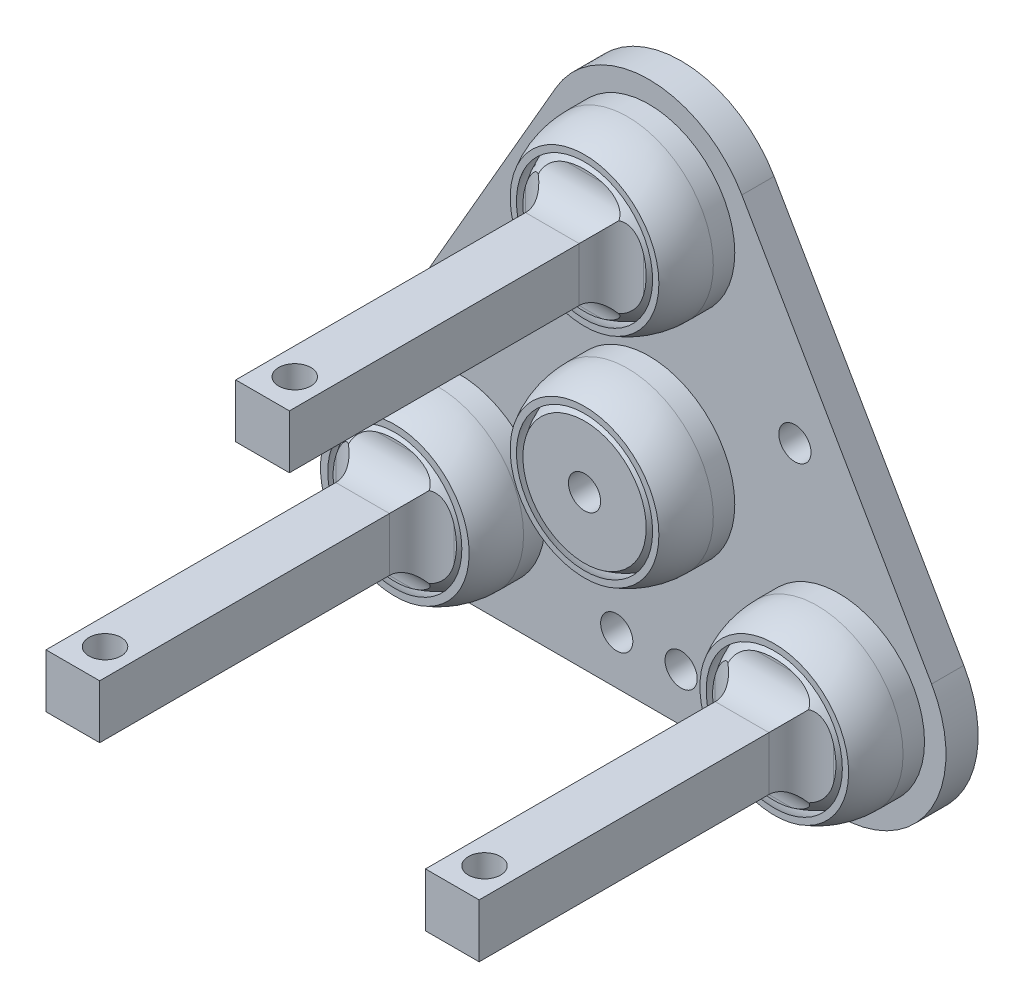
SolidWorks part; units mm, degrees
ref_plane "Front Plane" through (0, 0, 0) normal (0, 0, 1) x (1, 0, 0)
ref_plane "Top Plane" through (0, 0, 0) normal (0, 1, 0) x (1, 0, 0)
ref_plane "Right Plane" through (0, 0, 0) normal (1, 0, 0) x (0, 0, -1)
sketch "Sketch1" plane through (0, 0, 0) normal (0, 0, 1) x (1, 0, 0)
  line L0 (-39.7069, 0) -> (30.2931, 0)
  line L1 (30.2931, 0) -> (-4.7069, 60.6218)
  line L2 (-39.7069, 0) -> (-4.7069, 60.6218)
  dimension "D1" = 70
  dimension "D2" = 60
  dimension "D3" = 60
extrude "Boss-Extrude1" add sketch "Sketch1" along normal blind 3 contours L2 L0 L1 | L2 L0 L1 region at (-4.7069, 20.2073, 0)
sketch "Sketch4" plane through (0, 0, 3) normal (0, 0, 1) x (1, 0, 0)
  line L0 (-4.7069, 60.6218) -> (-4.7069, 40.6218) construction
  line L1 (-39.7069, 0) -> (-22.3864, 10) construction
  line L2 (30.2931, 0) -> (12.9726, 10) construction
  line L3 (-4.7069, 40.6218) -> (-4.7069, 0) construction
  line L4 (-39.7069, 0) -> (30.2931, 0) construction
  line L6 (12.9726, 10) -> (-22.2069, 30.3109) construction
  line L7 (-39.7069, 0) -> (-4.7069, 60.6218) construction
  line L8 (-28.743, 24.6509) -> (-42.7396, 47.6087) construction
  line L9 (-22.3864, 10) -> (12.7931, 30.3109) construction
  circle A0 centre (-22.3864, 10) radius 8
  circle A1 centre (-4.7069, 40.6218) radius 8
  circle A2 centre (12.9726, 10) radius 8
  circle A3 centre (-4.7069, 20.3109) radius 8
  dimension "D3" = 20
  dimension "D6" = 16
  dimension "D7" = 16
  dimension "D8" = 16
  dimension "D9" = 16
  dimension "D1" = 30
  dimension "D2" = 30
  dimension "D4" = 20
  dimension "D5" = 20
extrude "Boss-Extrude2" add sketch "Sketch4" along normal blind 2
sketch "Sketch5" plane through (0, 0, 5) normal (0, 0, 1) x (1, 0, 0)
  line L0 (-4.7069, 48.6218) -> (-4.7069, 32.6218)
  circle A0 centre (-4.7069, 40.6218) radius 8 construction
  circle A1 centre (-4.7069, 40.6218) radius 8 construction
  arc A2 (-4.7069, 48.6218) -> (-4.7069, 32.6218) centre (-4.7069, 40.6218) cw
revolve "Revolve3" add sketch "Sketch5" angle 360 about L0
sketch "Sketch6" plane through (0, 0, 5) normal (0, 0, 1) x (1, 0, 0)
  line L0 (-4.7069, 28.3109) -> (-4.7069, 12.3109)
  circle A0 centre (-4.7069, 20.3109) radius 8 construction
  circle A1 centre (-4.7069, 20.3109) radius 8 construction
  arc A2 (-4.7069, 28.3109) -> (-4.7069, 12.3109) centre (-4.7069, 20.3109) cw
revolve "Revolve4" add sketch "Sketch6" angle 360 about L0
sketch "Sketch7" plane through (0, 0, 5) normal (0, 0, 1) x (1, 0, 0)
  line L0 (-22.3864, 18) -> (-22.3864, 2)
  circle A0 centre (-22.3864, 10) radius 8 construction
  circle A1 centre (-22.3864, 10) radius 8 construction
  arc A2 (-22.3864, 18) -> (-22.3864, 2) centre (-22.3864, 10) cw
revolve "Revolve5" add sketch "Sketch7" angle 360 about L0
sketch "Sketch8" plane through (0, 0, 5) normal (0, 0, 1) x (1, 0, 0)
  line L0 (12.9726, 18) -> (12.9726, 2)
  circle A0 centre (12.9726, 10) radius 8 construction
  circle A1 centre (12.9726, 10) radius 8 construction
  arc A2 (12.9726, 18) -> (12.9726, 2) centre (12.9726, 10) cw
revolve "Revolve6" add sketch "Sketch8" angle 360 about L0
ref_plane "Plane2" through (0, 0, 13) normal (0, 0, -1) x (-1, 0, 0)
sketch "Sketch10" plane through (0, 0, 13) normal (0, 0, -1) x (-1, 0, 0)
  line L1 (34.5189, 52.9418) -> (-25.1051, 52.9418)
  line L2 (34.5189, 52.9418) -> (34.5189, -12.32)
  line L3 (34.5189, -12.32) -> (-25.1051, -12.32)
  line L4 (-25.1051, 52.9418) -> (-25.1051, -12.32)
  line L5 (34.5189, 52.9418) -> (-25.1051, -12.32) construction
  line L6 (34.5189, -12.32) -> (-25.1051, 52.9418) construction
  point P0 (4.7069, 20.3109)
extrude "Cut-Extrude1" cut sketch "Sketch10" along normal blind 4
ref_plane "Plane3" through (0, 0, 5) normal (0, 0, 1) x (1, 0, 0)
sketch "Sketch11" plane through (0, 0, 5) normal (0, 0, 1) x (1, 0, 0)
  line L0 (-4.7069, 48.1218) -> (-4.7069, 33.1218)
  circle A0 centre (-4.7069, 40.6218) radius 8 construction
  arc A1 (-4.7069, 48.1218) -> (-4.7069, 33.1218) centre (-4.7069, 40.6218) cw
  dimension "D2" = 7.5
  dimension "D1" = 15
revolve "Cut-Revolve1" cut sketch "Sketch11" angle 360 about L0
ref_plane "Plane4" through (0, 0, 5) normal (0, 0, 1) x (1, 0, 0)
sketch "Sketch12" plane through (0, 0, 5) normal (0, 0, 1) x (1, 0, 0)
  line L0 (-4.7069, 27.8109) -> (-4.7069, 12.8109)
  circle A0 centre (-4.7069, 20.3109) radius 8 construction
  arc A1 (-4.7069, 27.8109) -> (-4.7069, 12.8109) centre (-4.7069, 20.3109) cw
  dimension "D2" = 7.5
  dimension "D1" = 15
revolve "Cut-Revolve2" cut sketch "Sketch12" angle 360 about L0
ref_plane "Plane5" through (0, 0, 5) normal (0, 0, 1) x (1, 0, 0)
sketch "Sketch13" plane through (0, 0, 5) normal (0, 0, 1) x (1, 0, 0)
  line L0 (12.9726, 17.5) -> (12.9726, 2.5)
  circle A0 centre (12.9726, 10) radius 8 construction
  arc A1 (12.9726, 17.5) -> (12.9726, 2.5) centre (12.9726, 10) cw
  dimension "D1" = 15
  dimension "D2" = 7.5
revolve "Cut-Revolve3" cut sketch "Sketch13" angle 360 about L0
ref_plane "Plane6" through (0, 0, 5) normal (0, 0, 1) x (1, 0, 0)
sketch "Sketch14" plane through (0, 0, 5) normal (0, 0, 1) x (1, 0, 0)
  line L0 (-22.3864, 17.5) -> (-22.3864, 2.5)
  circle A0 centre (-22.3864, 10) radius 8 construction
  arc A1 (-22.3864, 17.5) -> (-22.3864, 2.5) centre (-22.4707, 10) cw
  dimension "D1" = 15
  dimension "D2" = 7.5
revolve "Cut-Revolve4" cut sketch "Sketch14" angle 360 about L0
sketch "Sketch16" plane through (0, 0, 5) normal (0, 0, 1) x (1, 0, 0)
  line L0 (-22.3864, 17) -> (-22.3864, 3)
  circle A0 centre (-22.3864, 10) radius 8 construction
  arc A1 (-22.3864, 17) -> (-22.3864, 3) centre (-22.3864, 10) cw
  dimension "D1" = 14
  dimension "D2" = 7
revolve "Revolve7" add sketch "Sketch16" angle 360 about L0
sketch "Sketch17" plane through (0, 0, 5) normal (0, 0, 1) x (1, 0, 0)
  line L0 (12.9726, 17) -> (12.9726, 3)
  circle A0 centre (12.9726, 10) radius 8 construction
  arc A1 (12.9726, 17) -> (12.9726, 3) centre (12.9726, 10) cw
  dimension "D1" = 14
  dimension "D2" = 7
revolve "Revolve8" add sketch "Sketch17" angle 360 about L0
sketch "Sketch18" plane through (0, 0, 5) normal (0, 0, 1) x (1, 0, 0)
  line L0 (-4.7069, 27.3109) -> (-4.7069, 13.3109)
  circle A0 centre (-4.7069, 20.3109) radius 8 construction
  arc A1 (-4.7069, 27.3109) -> (-4.7069, 13.3109) centre (-4.7069, 20.3109) cw
  dimension "D3" = 7
  dimension "D1" = 14
  dimension "D2" = 7
revolve "Revolve9" add sketch "Sketch18" angle 360 about L0
sketch "Sketch19" plane through (0, 0, 5) normal (0, 0, 1) x (1, 0, 0)
  line L0 (-4.7069, 47.6218) -> (-4.7069, 33.6218)
  circle A0 centre (-4.7069, 40.6218) radius 8 construction
  arc A1 (-4.7069, 47.6218) -> (-4.7069, 33.6218) centre (-4.7069, 40.6218) cw
  dimension "D3" = 7
  dimension "D1" = 14
  dimension "D2" = 7
revolve "Revolve10" add sketch "Sketch19" angle 360 about L0
sketch "Sketch20" plane through (0, 0, 9) normal (0, 0, 1) x (1, 0, 0)
  line L1 (-44.0878, 97.9698) -> (34.674, 97.9698)
  line L2 (-44.0878, 97.9698) -> (-44.0878, -2.8698)
  line L3 (-44.0878, -2.8698) -> (34.674, -2.8698)
  line L4 (34.674, 97.9698) -> (34.674, -2.8698)
  line L5 (-44.0878, 97.9698) -> (34.674, -2.8698) construction
  line L6 (-44.0878, -2.8698) -> (34.674, 97.9698) construction
  circle A0 centre (-4.7069, 40.6218) radius 6.9282 construction
  point P0 (-4.7069, 47.55)
extrude "Cut-Extrude2" cut sketch "Sketch20" along normal blind 11
sketch "Sketch21" plane through (0, 0, 0) normal (0, 0, -1) x (-1, 0, 0)
  line L1 (-26.6658, 56.1395) -> (35.9916, 56.1395)
  line L2 (-26.6658, 56.1395) -> (-26.6658, 1.9303)
  line L3 (-26.6658, 1.9303) -> (35.9916, 1.9303)
  line L4 (35.9916, 56.1395) -> (35.9916, 1.9303)
  line L5 (-26.6658, 56.1395) -> (35.9916, 1.9303) construction
  line L6 (-26.6658, 1.9303) -> (35.9916, 56.1395) construction
  point P0 (4.6629, 29.0349)
extrude "Cut-Extrude3" cut sketch "Sketch21" along normal blind 8
sketch "Sketch22" plane through (0, 0, 3) normal (0, 0, 1) x (1, 0, 0)
  line L2 (-39.7069, 0) -> (30.2931, 0) construction
  line L3 (30.2931, 0) -> (-4.7069, 60.6218) construction
  line L4 (-39.7069, 0) -> (-4.7069, 60.6218) construction
  circle A0 centre (-7.7069, 4.5) radius 1.5
  circle A1 centre (-1.7069, 4.5) radius 1.5
  circle A2 centre (8.896, 28.0609) radius 1.5
  circle A3 centre (-18.3098, 28.0609) radius 1.5
  point P0 (-4.7069, 0)
  point P1 (-4.7069, 0)
  point P4 (12.7931, 30.3109)
  point P16 (-22.2069, 30.3109)
  dimension "D1" = 4.5
  dimension "D3" = 3
  dimension "D4" = 3
  dimension "D7" = 3
  dimension "D8" = 4.5
  dimension "D5" = 3
  dimension "D2" = 4.5
  dimension "D6" = 3
  dimension "D9" = 3
  dimension "D10" = 4.5
extrude "Cut-Extrude4" cut sketch "Sketch22" against normal blind 8
sketch "Sketch23" plane through (0, 0, 9) normal (0, 0, 1) x (1, 0, 0)
  line L1 (10.4726, 12.5) -> (15.4726, 12.5)
  line L2 (10.4726, 12.5) -> (10.4726, 7.5)
  line L3 (10.4726, 7.5) -> (15.4726, 7.5)
  line L4 (15.4726, 12.5) -> (15.4726, 7.5)
  line L5 (10.4726, 12.5) -> (15.4726, 7.5) construction
  line L6 (10.4726, 7.5) -> (15.4726, 12.5) construction
  line L7 (-24.8864, 12.5) -> (-19.8864, 12.5)
  line L8 (-24.8864, 12.5) -> (-24.8864, 7.5)
  line L9 (-24.8864, 7.5) -> (-19.8864, 7.5)
  line L10 (-19.8864, 12.5) -> (-19.8864, 7.5)
  line L11 (-24.8864, 12.5) -> (-19.8864, 7.5) construction
  line L12 (-24.8864, 7.5) -> (-19.8864, 12.5) construction
  line L13 (-7.2069, 43.1218) -> (-2.2069, 43.1218)
  line L14 (-7.2069, 43.1218) -> (-7.2069, 38.1218)
  line L15 (-7.2069, 38.1218) -> (-2.2069, 38.1218)
  line L16 (-2.2069, 43.1218) -> (-2.2069, 38.1218)
  line L17 (-7.2069, 43.1218) -> (-2.2069, 38.1218) construction
  line L18 (-7.2069, 38.1218) -> (-2.2069, 43.1218) construction
  circle A1 centre (12.9726, 10) radius 5.7446 construction
  circle A2 centre (-22.3864, 10) radius 5.7446 construction
  circle A3 centre (-4.7069, 40.6218) radius 5.7446 construction
  point P0 (12.9726, 10)
  point P7 (-22.3864, 10)
  point P14 (-4.7069, 40.6218)
  dimension "D4" = 5
  dimension "D6" = 0
  dimension "D9" = 0
  dimension "D11" = 0
  dimension "D12" = 0
  dimension "D2" = 5
  dimension "D3" = 5
  dimension "D5" = 5
  dimension "D7" = 5
  dimension "D8" = 5
  dimension "D10" = 0
extrude "Boss-Extrude3" add sketch "Sketch23" along normal blind 30
sketch "Sketch24" plane through (0, 0, 9) normal (0, 0, 1) x (1, 0, 0)
  circle A0 centre (-4.7069, 20.3109) radius 1.5
  dimension "D1" = 3
extrude "Cut-Extrude5" cut sketch "Sketch24" against normal blind 30
sketch "Sketch25" plane through (0, 7.5, 0) normal (0, -1, 0) x (1, 0, 0)
  line L0 (-24.8864, 39) -> (-19.8864, 39) construction
  line L1 (-7.2069, 39) -> (-2.2069, 39) construction
  line L2 (10.4726, 39) -> (15.4726, 39) construction
  circle A0 centre (-22.3864, 36) radius 1.5
  circle A1 centre (-4.7069, 36) radius 1.5
  circle A2 centre (12.9726, 36) radius 1.5
  dimension "D1" = 3
  dimension "D2" = 3
  dimension "D3" = 3
  dimension "D4" = 3
  dimension "D5" = 3
  dimension "D6" = 3
extrude "Cut-Extrude6" cut sketch "Sketch25" against normal blind 37
fillet "Fillet1" radius 3 4 edges at (-4.7069, 43.1218, 9) (-2.2069, 40.6218, 9) (-4.7069, 38.1218, 9) (-7.2069, 40.6218, 9) type face fillet first side face at (-4.7069, 38.1218, 37.5) first side face at (-7.2069, 40.6218, 24) first side face at (-2.2069, 40.6218, 24) first side face at (-4.7069, 43.1218, 34.5) second side face at (1.0377, 40.6218, 9)
fillet "Fillet2" radius 3 4 edges at (-22.3864, 12.5, 9) (-19.8864, 10, 9) (-22.3864, 7.5, 9) (-24.8864, 10, 9) type face fillet first side face at (-22.3864, 12.5, 34.5) first side face at (-19.8864, 10, 24) first side face at (-22.3864, 7.5, 34.5) first side face at (-24.8864, 10, 24) second side face at (-16.6418, 10, 9)
fillet "Fillet3" radius 3 4 edges at (12.9726, 12.5, 9) (15.4726, 10, 9) (12.9726, 7.5, 9) (10.4726, 10, 9) type face fillet first side face at (12.9726, 12.5, 34.5) first side face at (15.4726, 10, 24) first side face at (10.4726, 10, 24) first side face at (12.9726, 7.5, 34.5) second side face at (18.7172, 10, 9)
fillet "Fillet4" radius 10 1 edges at (30.2931, 0, 1.5)
fillet "Fillet5" radius 10 1 edges at (-4.7069, 60.6218, 1.5)
fillet "Fillet6" radius 10 1 edges at (-39.7069, 0, 1.5)
